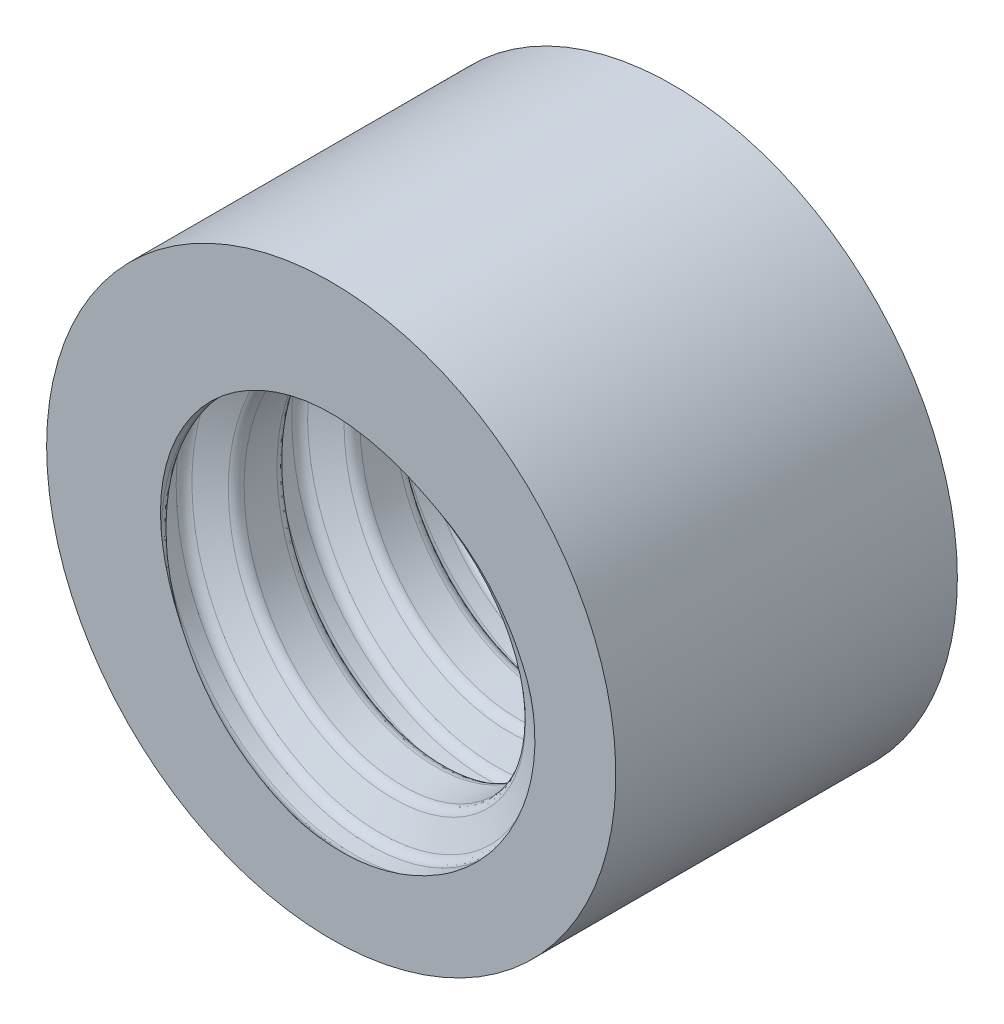
SolidWorks part; units mm, degrees
ref_plane "Front Plane" through (0, 0, 0) normal (0, 0, 1) x (1, 0, 0)
ref_plane "Top Plane" through (0, 0, 0) normal (0, 1, 0) x (1, 0, 0)
ref_plane "Right Plane" through (0, 0, 0) normal (1, 0, 0) x (0, 0, -1)
sketch "Sketch1" plane through (0, 0, 0) normal (0, 0, 1) x (1, 0, 0)
  circle A0 centre (0, 0) radius 7.5
  circle A1 centre (0, 0) radius 12.5
  dimension "D1" = 15
  dimension "D2" = 25
extrude "Boss-Extrude1" add sketch "Sketch1" along normal blind 20
thread "Thread1" pitch 5.08 method cut profile "Thread Profile1" start angle 0, offset 0, length 0, pitch 5.08, diameter 15
ref_plane "Plane1" through (-7.5, 0, 20) normal (0, -1, 0) x (-1, 0, 0)
sketch "Thread Profile1" plane through (-7.5, 0, 20) normal (0, -1, 0) x (-1, 0, 0)
  line L0 (0, 0) -> (0, 5.08) construction
  line L1 (0, 0) -> (0, 3.6346)
  line L2 (0.508, 3.6346) -> (1.524, 3.6346) construction
  line L3 (1.524, 2.1681) -> (1.524, 1.4665)
  line L4 (1.27, 2.6081) -> (0.254, 3.1946)
  line L5 (1.27, 1.0265) -> (0.254, 0.4399)
  line L6 (0.508, 0) -> (1.524, 0) construction
  arc A0 (0.254, 3.1946) -> (0, 3.6346) centre (0.508, 3.6346) cw
  arc A1 (0.254, 0.4399) -> (0, 0) centre (0.508, 0) ccw
  arc A2 (1.524, 1.4665) -> (1.27, 1.0265) centre (1.016, 1.4665) cw
  arc A3 (1.524, 2.1681) -> (1.27, 2.6081) centre (1.016, 2.1681) ccw
  point P10 (1.524, 2.4614)
  point P17 (1.524, 1.1732)
  point P18 (0, 3.3413)
  point P19 (0, 0.2933)
  point P20 (0, 0)
  dimension "RootFillet1" = 0.508
  dimension "RootFillet2" = 0.508
  dimension "CrestFillet2" = 0.508
  dimension "CrestFillet1" = 0.508
  dimension "Pitch" = 5.08
  dimension "Angle1" = 30
  dimension "Angle2" = 30
  dimension "a" = 3.048
  dimension "b" = 1.524
  dimension "c" = 1.2882
sketch "Sketch6" plane through (0, 0, 0) normal (0, 1, 0) x (1, 0, 0)
  line L0 (-12.5, -20) -> (12.5, -20) construction
  line L1 (-12.5, -25) -> (12.5, -25)
  line L2 (-12.5, -25) -> (-12.5, -15)
  line L3 (-12.5, -15) -> (12.5, -15)
  line L4 (12.5, -25) -> (12.5, -15)
  line L5 (-12.5, -25) -> (12.5, -15) construction
  line L6 (-12.5, -15) -> (12.5, -25) construction
  line L7 (-12.5, 0) -> (-12.5, -20) construction
  point P0 (0, -20)
  dimension "D1" = 10
extrude "Cut-Extrude1" cut sketch "Sketch6" against normal through all both and the other way through all
